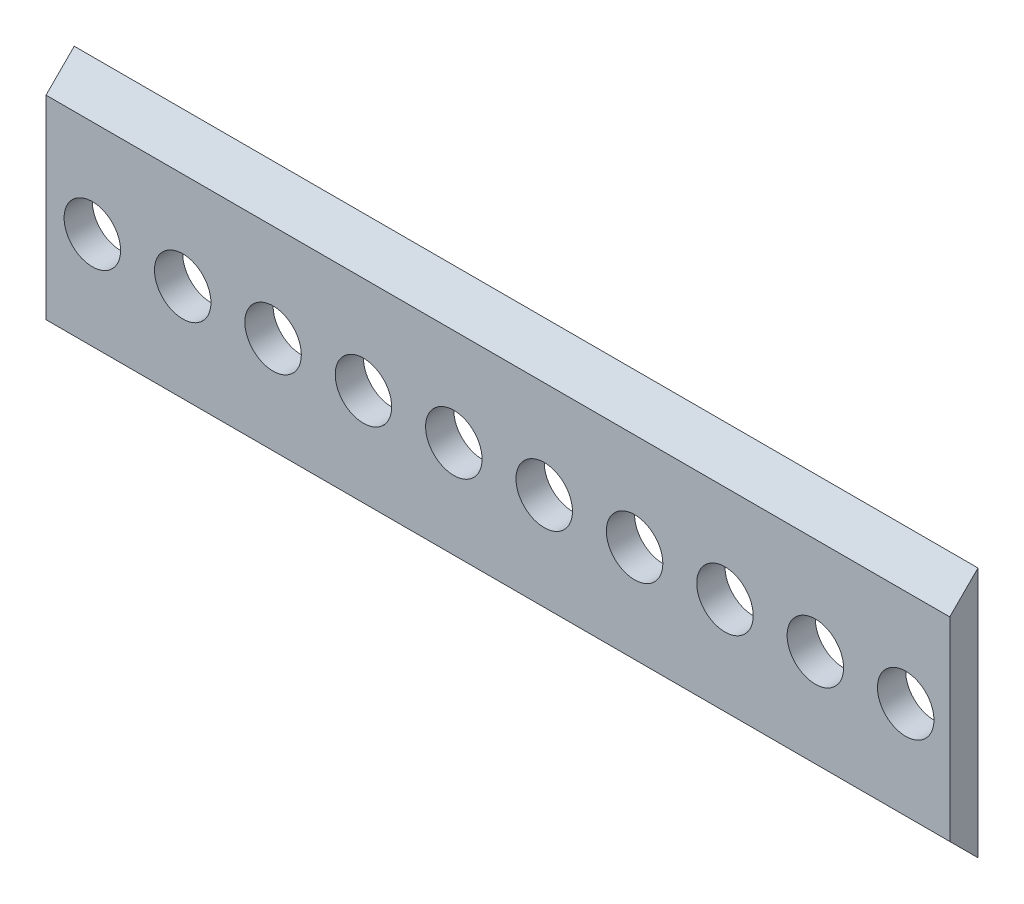
SolidWorks part; units mm, degrees
ref_plane "Front Plane" through (0, 0, 0) normal (0, 0, 1) x (1, 0, 0)
ref_plane "Top Plane" through (0, 0, 0) normal (0, 1, 0) x (1, 0, 0)
ref_plane "Right Plane" through (0, 0, 0) normal (1, 0, 0) x (0, 0, -1)
sketch "Sketch1" plane through (0, 0, 0) normal (0, 0, 1) x (1, 0, 0)
  line L0 (0, 28.2153) -> (0, 0)
  line L1 (0, 0) -> (101.6, 0)
  line L2 (101.6, 0) -> (101.6, 28.2153)
  line L3 (101.6, 28.2153) -> (0, 28.2153)
  line L4 (5.2076, 14.1076) -> (96.6476, 14.1076) construction
  line L5 (5.2076, 14.1076) -> (0, 14.1076) construction
  circle A0 centre (5.2076, 14.1076) radius 3.175
  circle A1 centre (15.3676, 14.1076) radius 3.175
  circle A2 centre (25.5276, 14.1076) radius 3.175
  circle A3 centre (35.6876, 14.1076) radius 3.175
  circle A4 centre (45.8476, 14.1076) radius 3.175
  circle A5 centre (56.0076, 14.1076) radius 3.175
  circle A6 centre (66.1676, 14.1076) radius 3.175
  circle A7 centre (76.3276, 14.1076) radius 3.175
  circle A8 centre (86.4876, 14.1076) radius 3.175
  circle A9 centre (96.6476, 14.1076) radius 3.175
  dimension "D15" = 6.35
  dimension "D1" = 28.2153
  dimension "D2" = 101.6
  dimension "D3" = 5.2076
  dimension "D4" = 10.16
  dimension "D5" = 10.16
  dimension "D6" = 10.16
  dimension "D7" = 10.16
  dimension "D8" = 10.16
  dimension "D9" = 10.16
  dimension "D10" = 10.16
  dimension "D11" = 10.16
  dimension "D12" = 10.16
  dimension "D13" = 4.9524
extrude "Boss-Extrude1" add sketch "Sketch1" along normal blind 3.175 contours L2 L3 L0 L1 A0 A1 A2 A3 A4 A5 A6 A7 A8 A9 region at (50.7841, 14.1076, 0)
chamfer "Chamfer1" distance 3.175 angle 45 2 edges at (50.8, 0, 3.175) (50.8, 28.2153, 3.175)
